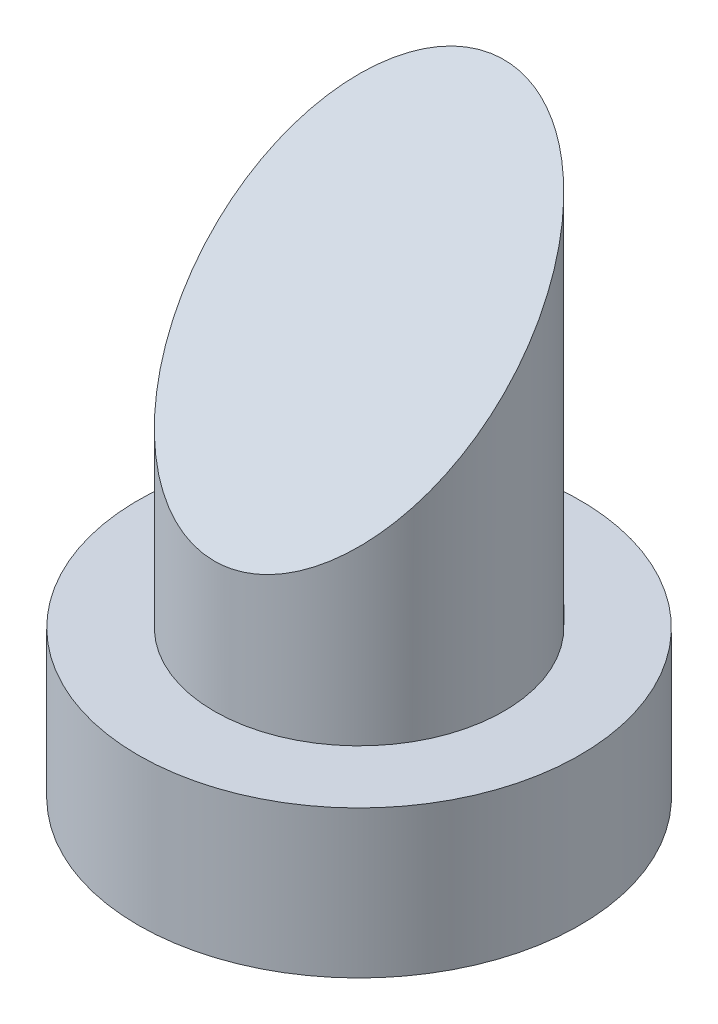
SolidWorks part; units mm, degrees
material "OMD-98"
ref_plane "Front Plane" through (0, 0, 0) normal (0, 0, 1) x (1, 0, 0)
ref_plane "Top Plane" through (0, 0, 0) normal (0, 1, 0) x (1, 0, 0)
ref_plane "Right Plane" through (0, 0, 0) normal (1, 0, 0) x (0, 0, -1)
sketch "Sketch1" plane through (0, 0, 0) normal (0, 1, 0) x (1, 0, 0)
  circle A0 centre (0, 0) radius 9
  dimension "D1" = 18
extrude "Boss-Extrude1" add sketch "Sketch1" along normal blind 6
sketch "Sketch2" plane through (0, 6, 0) normal (0, 1, 0) x (1, 0, 0)
  circle A0 centre (0, 0) radius 5.9
  dimension "D1" = 11.8
extrude "Boss-Extrude2" add sketch "Sketch2" along normal blind 20
sketch "Sketch3" plane through (0, 0, 0) normal (1, 0, 0) x (0, 0, -1)
  line L0 (-6.28, 10.92) -> (6.28, 23.48)
  line L2 (9, 6) -> (-9, 6) construction
  line L4 (-6.28, 10.92) -> (-6.28, 28.7719)
  line L5 (-6.28, 28.7719) -> (6.28, 28.7719)
  line L6 (6.28, 23.48) -> (6.28, 28.7719)
  point P2 (0, 17.2)
  dimension "D1" = 12.56
  dimension "D2" = 45
  dimension "D3" = 12.56
  dimension "D4" = 6.28
  dimension "D5" = 11.2
extrude "Cut-Extrude1" cut sketch "Sketch3" against normal through all both and the other way through all contours L0 L6 L5 L4 region at (0, 22.4179, 1.136)
sketch "Sketch4" plane through (0, 0, 0) normal (0, -1, 0) x (1, 0, 0)
  circle A0 centre (0, -6) radius 0.5
  dimension "D1" = 1
  dimension "D2" = 6
extrude "Cut-Extrude2" cut sketch "Sketch4" against normal blind 1.5
